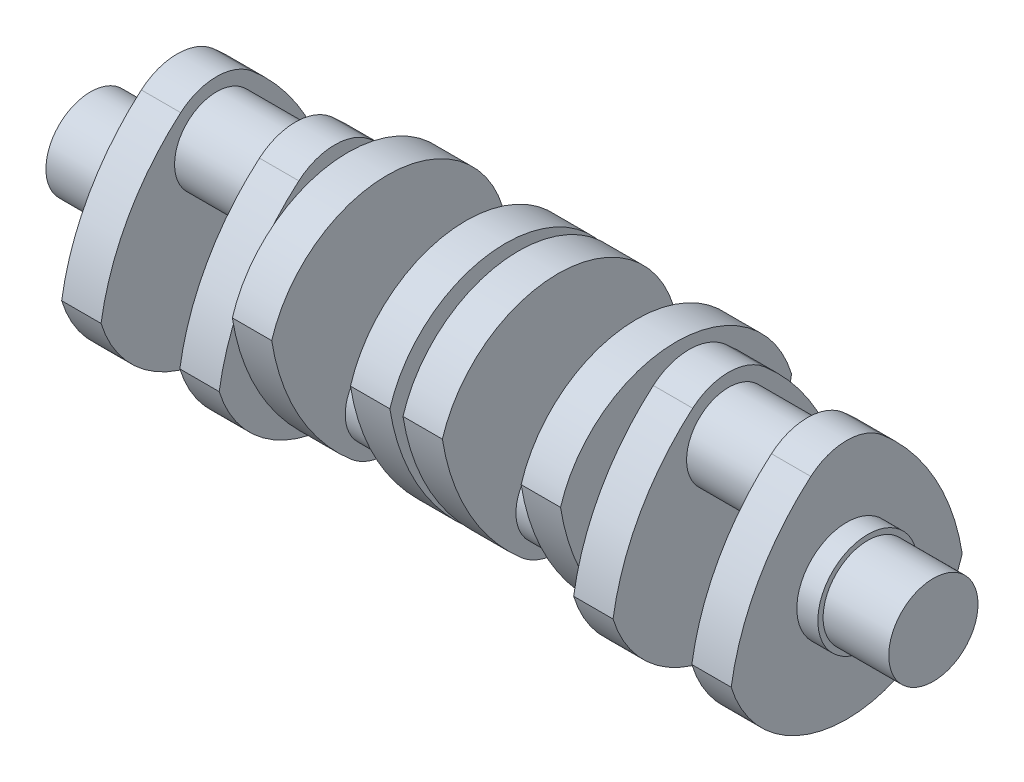
SolidWorks part; units mm, degrees
ref_plane "Front Plane" through (0, 0, 0) normal (0, 0, 1) x (1, 0, 0)
ref_plane "Top Plane" through (0, 0, 0) normal (0, 1, 0) x (1, 0, 0)
ref_plane "Right Plane" through (0, 0, 0) normal (1, 0, 0) x (0, 0, -1)
sketch "Sketch1" plane through (0, 0, 0) normal (1, 0, 0) x (0, 0, -1)
  circle A0 centre (0, 0) radius 19
  circle A1 centre (0, 0) radius 17
  dimension "D1" = 38
  dimension "D2" = 34
extrude "Boss-Extrude1" add sketch "Sketch1" against normal blind 25 contours A1 region at (0, 0, 0)
extrude "Boss-Extrude2" add sketch "Sketch1<3>" along normal blind 8 contours A1 | A0 A1 region at (0, 0, 18.4626) region at (0, 0, 0)
sketch "Sketch1<3>" plane through (0, 0, 0) normal (1, 0, 0) x (0, 0, -1) same geometry as "Sketch1"
sketch "Sketch2" plane through (8, 0, 0) normal (1, 0, 0) x (0, 0, -1)
  arc A4 (-13.6681, 40.9431) -> (13.6681, 40.9431) centre (0, 25) cw
  arc A5 (-44, -13.4164) -> (44, -13.4164) centre (0, 0) ccw
  arc A6 (-44, -13.4164) -> (-13.6681, 40.9431) centre (44.9095, -27.3845) cw
  arc A7 (13.6681, 40.9431) -> (44, -13.4164) centre (-44.9095, -27.3845) cw
  dimension "D3" = 46
  dimension "D4" = 21
  dimension "D5" = 90
  dimension "D6" = 90
  dimension "D1" = 25
  dimension "D2" = 88
extrude "Boss-Extrude3" add sketch "Sketch2" along normal blind 15
sketch "Sketch3" plane through (23, 0, 0) normal (1, 0, 0) x (0, 0, -1)
  circle A0 centre (0, 25) radius 16
  dimension "D1" = 32
extrude "Boss-Extrude4" add sketch "Sketch3" along normal blind 15
mirror "Mirror1" about plane through (38, 25, 0) normal (1, 0, 0) of "Boss-Extrude3", "Boss-Extrude4"
sketch "Sketch4" plane through (68, 0, 0) normal (1, 0, 0) x (0, 0, -1)
  circle A0 centre (0, 0) radius 17
  dimension "D1" = 34
extrude "Boss-Extrude5" add sketch "Sketch4" along normal blind 5
sketch "Sketch5" plane through (73, 0, 0) normal (1, 0, 0) x (0, 0, -1)
  arc A8 (-13.6681, -40.9431) -> (13.6681, -40.9431) centre (0, -25) ccw
  arc A9 (-44, 13.4164) -> (-13.6681, -40.9431) centre (44.9095, 27.3845) ccw
  arc A10 (44, 13.4164) -> (-44, 13.4164) centre (0, 0) ccw
  arc A11 (13.6681, -40.9431) -> (44, 13.4164) centre (-44.9095, 27.3845) ccw
extrude "Boss-Extrude6" add sketch "Sketch5" along normal blind 15
sketch "Sketch6" plane through (88, 0, 0) normal (1, 0, 0) x (0, 0, -1)
  circle A1 centre (0, -25) radius 16
  dimension "D1" = 32
  dimension "D2" = 25
extrude "Boss-Extrude7" add sketch "Sketch6" along normal blind 30
sketch "Sketch7" plane through (118, 0, 0) normal (1, 0, 0) x (0, 0, -1)
  arc A4 (-13.6681, -40.9431) -> (13.6681, -40.9431) centre (0, -25) ccw
  arc A5 (13.6681, -40.9431) -> (44, 13.4164) centre (-44.9095, 27.3845) ccw
  arc A6 (44, 13.4164) -> (-44, 13.4164) centre (0, 0) ccw
  arc A7 (-44, 13.4164) -> (-13.6681, -40.9431) centre (44.9095, 27.3845) ccw
  arc A8 (-13.6681, -40.9431) -> (13.6681, -40.9431) centre (0, -25) ccw
  arc A9 (13.6681, -40.9431) -> (44, 13.4164) centre (-44.9095, 27.3845) ccw
  arc A10 (44, 13.4164) -> (-44, 13.4164) centre (0, 0) ccw
  arc A11 (-44, 13.4164) -> (-13.6681, -40.9431) centre (44.9095, 27.3845) ccw
  dimension "D1" = 0
extrude "Boss-Extrude8" add sketch "Sketch7" along normal blind 15
sketch "Sketch8" plane through (133, 0, 0) normal (1, 0, 0) x (0, 0, -1)
  circle A0 centre (0, 0) radius 17
  dimension "D1" = 34
extrude "Boss-Extrude9" add sketch "Sketch8" along normal blind 2.5
mirror "Mirror2" about plane through (135.5, 0, 0) normal (1, 0, 0) of bodies 110
